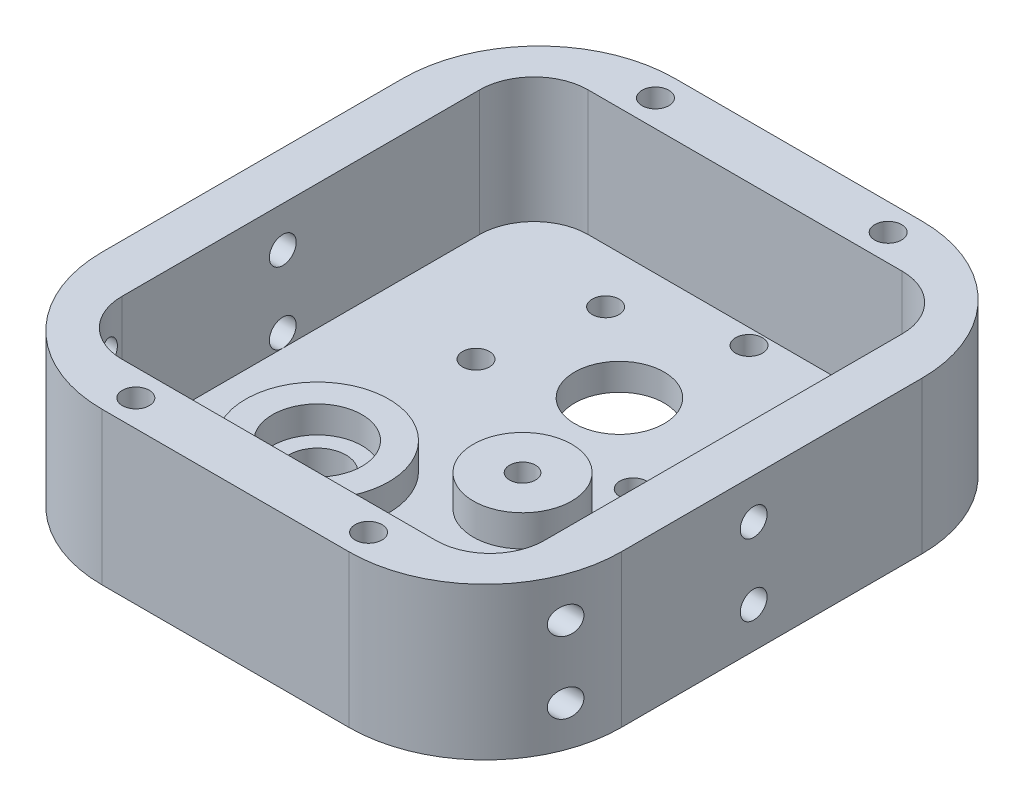
SolidWorks part; units mm, degrees
ref_plane "Front Plane" through (0, 0, 0) normal (0, 0, 1) x (1, 0, 0)
ref_plane "Top Plane" through (0, 0, 0) normal (0, 1, 0) x (1, 0, 0)
ref_plane "Right Plane" through (0, 0, 0) normal (1, 0, 0) x (0, 0, -1)
sketch "Sketch1" plane through (0, 0, 0) normal (0, 1, 0) x (1, 0, 0)
  line L0 (0, 0) -> (5.3232, -16.1451) construction
  line L1 (5.3232, -16.1451) -> (-9.7532, -24) construction
  line L2 (-9.7532, -24) -> (0, 0) construction
  line L3 (-29, -28.7775) -> (-29, 4.7775)
  line L4 (29, -28.7775) -> (29, 4.7775)
  line L5 (-13.7775, -44) -> (13.7775, -44)
  line L6 (-13.7775, 20) -> (13.7775, 20)
  line L7 (0, 0) -> (0, -69.1065) construction
  circle A2 centre (0, 0) radius 6.5 construction
  circle A4 centre (-9.7532, -24) radius 12 construction
  circle A5 centre (5.3232, -16.1451) radius 12 construction
  circle A6 centre (5.3232, -16.1451) radius 6.5 construction
  circle A7 centre (-9.7532, -24) radius 3.2
  circle A13 centre (0, 0) radius 5
  circle A15 centre (5.3232, -16.1451) radius 5.5
  circle A16 centre (-9.7532, -24) radius 5
  circle A17 centre (-9.7532, -24) radius 8
  circle A18 centre (0, 0) radius 18 construction
  arc A23 (-29, 4.7775) -> (-13.7775, 20) centre (-13.7775, 4.7775) cw
  arc A24 (13.7775, 20) -> (29, 4.7775) centre (13.7775, 4.7775) cw
  arc A25 (-29, -28.7775) -> (-13.7775, -44) centre (-13.7775, -28.7775) ccw
  arc A26 (13.7775, -44) -> (29, -28.7775) centre (13.7775, -28.7775) ccw
  circle A28 centre (5.3232, -16.1451) radius 1.45
  point P1 (-7.2248, -16.4864)
  point P10 (-4.8766, -12)
  point P13 (-9.7532, -20.8)
  point P15 (-9.7532, -36)
  point P27 (0, 18)
  point P31 (0, -44)
  point P33 (-29, -12)
  point P43 (0, 20)
  dimension "D2" = 17
  dimension "D3" = 13
  dimension "D4" = 17
  dimension "D5" = 6.4
  dimension "D6" = 24
  dimension "D9" = 58
  dimension "D10" = 64
  dimension "D11" = 11
  dimension "D12" = 2.9
  dimension "D13" = 3
  dimension "D7" = 36
  dimension "D8" = 5
  dimension "D14" = 2
extrude "Boss-Extrude1" add sketch "Sketch1" along normal blind 3 contours L5 A26 L4 A24 L6 A23 L3 A25 A13 A15 A17 | A15 | A17 A16 | A16 A7 region at (0.4636, 0, 11.406) region at (-0.0212, 0, 16.1451) region at (-14.6118, 0, 24) region at (-17.527, 0, 24)
sketch "Sketch2" plane through (0, 0, 0) normal (0, 1, 0) x (1, 0, 0)
  line L0 (0, 0) -> (50.7044, 0) construction
  line L1 (0, 0) -> (11.7462, 4.2753) construction
  circle A0 centre (0, 0) radius 12.5 construction
  circle A7 centre (11.7462, 4.2753) radius 1.5
  circle A8 centre (9.5756, -8.0348) radius 1.5
  circle A9 centre (-2.1706, -12.3101) radius 1.5
  circle A10 centre (-11.7462, -4.2753) radius 1.5
  circle A11 centre (-9.5756, 8.0348) radius 1.5
  circle A12 centre (2.1706, 12.3101) radius 1.5
  point P17 (0, 0)
  dimension "D1" = 25
  dimension "D2" = 20
  dimension "D3" = 3
  dimension "D4" = 6
extrude "Boss-Extrude2" add sketch "Sketch1<4>" along normal blind 6.5 contours A15 region at (-0.0212, 0, 16.1451)
sketch "Sketch1<4>" plane through (0, 0, 0) normal (0, 1, 0) x (1, 0, 0) same geometry as "Sketch1"
extrude "Boss-Extrude3" add sketch "Sketch1<5>" along normal blind 6 contours A17 A16 region at (-17.527, 0, 24)
sketch "Sketch1<5>" plane through (0, 0, 0) normal (0, 1, 0) x (1, 0, 0) same geometry as "Sketch1"
sketch "Sketch3" plane through (0, 0, 0) normal (0, 1, 0) x (1, 0, 0)
  line L0 (0, 20) -> (0, -44) construction
  line L1 (-13.7775, 20) -> (13.7775, 20) construction
  line L6 (-13.7775, -44) -> (13.7775, -44) construction
  line L7 (-21.9186, 12.1861) -> (21.9186, -36.1861) construction
  line L13 (-13.7775, -44) -> (13.7775, -44)
  line L14 (-29, -28.7775) -> (-29, 4.7775)
  line L16 (-13.7775, 20) -> (13.7775, 20)
  line L17 (29, -28.7775) -> (29, 4.7775)
  line L19 (0, -12) -> (51.56, -12) construction
  line L20 (-17.5461, -38.0496) -> (17.5461, -38.0496)
  line L21 (-23.6075, -31.9883) -> (-23.6075, 7.9883)
  line L22 (-17.5461, 14.0496) -> (17.5461, 14.0496)
  line L23 (23.6075, -31.9883) -> (23.6075, 7.9883)
  line L24 (-21.9186, -36.1861) -> (21.9186, 12.1861) construction
  line L25 (-21.9186, 12.1861) -> (21.9186, -36.1861) construction
  line L26 (-21.9186, -36.1861) -> (21.9186, 12.1861) construction
  arc A9 (-29, 4.7775) -> (-13.7775, 20) centre (-13.7775, 4.7775) cw
  arc A10 (13.7775, 20) -> (29, 4.7775) centre (13.7775, 4.7775) cw
  arc A11 (29, -28.7775) -> (13.7775, -44) centre (13.7775, -28.7775) cw
  arc A12 (-13.7775, -44) -> (-29, -28.7775) centre (-13.7775, -28.7775) cw
  arc A13 (17.5461, 14.0496) -> (23.6075, 7.9883) centre (17.5461, 7.9883) cw
  arc A14 (-17.5461, 14.0496) -> (-23.6075, 7.9883) centre (-17.5461, 7.9883) ccw
  arc A15 (-17.5461, -38.0496) -> (-23.6075, -31.9883) centre (-17.5461, -31.9883) cw
  arc A16 (17.5461, -38.0496) -> (23.6075, -31.9883) centre (17.5461, -31.9883) ccw
  point P8 (0, -12)
  point P10 (0, -12)
extrude "Boss-Extrude4" add sketch "Sketch3" along normal blind 17
sketch "Sketch4" plane through (0, 17, 0) normal (0, 1, 0) x (1, 0, 0)
  line L0 (0, 14.0496) -> (0, 20) construction
  line L1 (-13.7775, 20) -> (13.7775, 20) construction
  line L2 (-13, 17.0248) -> (13, 17.0248) construction
  line L3 (-4.8766, -12) -> (49.0411, -12) construction
  line L4 (-13, -41.0248) -> (13, -41.0248) construction
  line L5 (0, -38.0496) -> (0, -44) construction
  line L7 (17.5461, 14.0496) -> (-17.5461, 14.0496) construction
  circle A0 centre (13, 17.0248) radius 1.5
  circle A1 centre (-13, 17.0248) radius 1.5
  circle A2 centre (-13, -41.0248) radius 1.5
  circle A3 centre (13, -41.0248) radius 1.5
  point P8 (0, 17.0248)
  point P19 (0, -41.0248)
  dimension "D1" = 3
  dimension "D2" = 26
extrude "Cut-Extrude2" cut sketch "Sketch4" against normal up to surface (14 mm away) up to face at (0, 3, 12)
extrude "Cut-Extrude4" cut sketch "Sketch2" along normal up to surface (3 mm away) contours A12 | A11 | A10 | A9 | A7 | A8 region at (-11.7462, 0, 4.2753) region at (-9.5756, 0, -8.0348) region at (2.1706, 0, -12.3101) up to face at (0, 3, 12)
sketch "Sketch5" plane through (29, 0, 0) normal (1, 0, 0) x (0, 0, -1)
  line L0 (20, 8.5) -> (-59.9226, 8.5) construction
  line L1 (20, 17) -> (20, 0) construction
  line L2 (-34, 8.5) -> (-14, 8.5) construction
  line L3 (-34, 4.5) -> (-34, 12.5) construction
  line L4 (-14, 4.5) -> (-14, 12.5) construction
  line L6 (-44, 17) -> (-44, 0) construction
  circle A0 centre (-34, 12.5) radius 1.5
  circle A1 centre (-34, 4.5) radius 1.5
  circle A2 centre (-14, 4.5) radius 1.5
  circle A3 centre (-14, 12.5) radius 1.5
  point P3 (-14.2118, 8.4224)
  point P11 (-34, 8.5)
  point P17 (0, 0)
  point P19 (-14, 8.5)
  dimension "D2" = 3
  dimension "D1" = 20
  dimension "D3" = 8
  dimension "D4" = 10
extrude "Cut-Extrude5" cut sketch "Sketch5" against normal blind 8
mirror "Mirror1" about plane through (0, 0, 0) normal (1, 0, 0) of "Cut-Extrude5"
